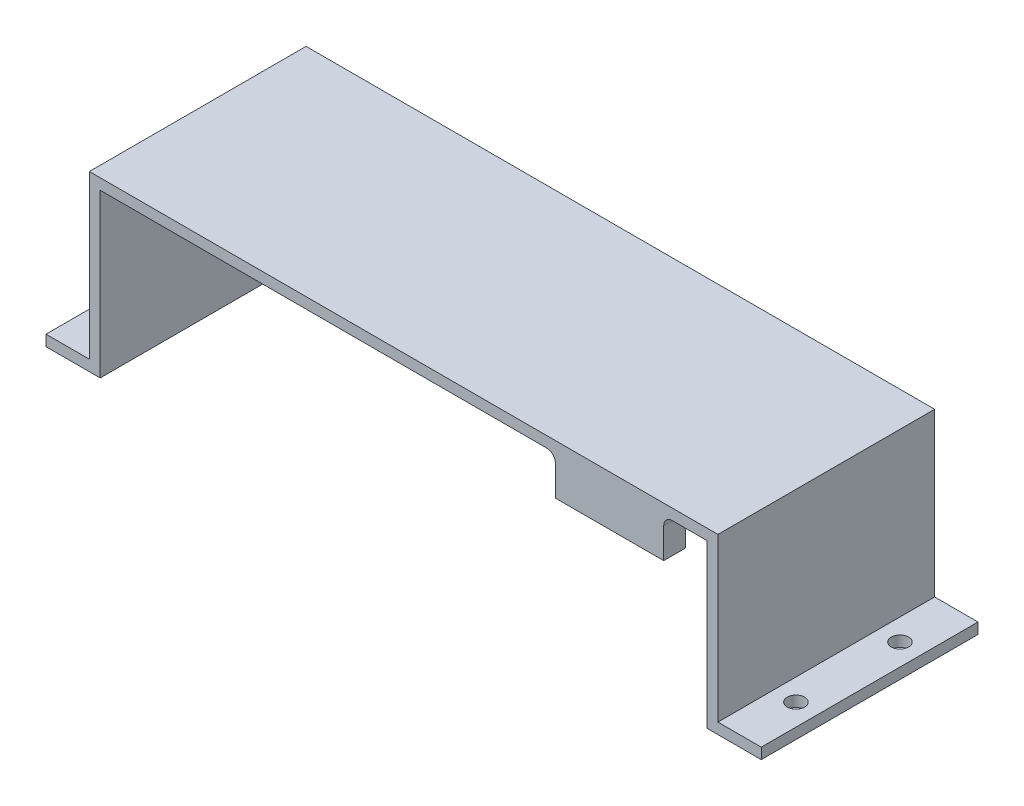
SolidWorks part; units mm, degrees
other "Markup1"
sketch "Sketch8" plane through (104.775, 3.175, 31.75) normal (0.0545, 0.0227, 0.9983) x (-0.9792, -0.1942, 0.0579)
ref_plane "Front Plane" through (0, 0, 0) normal (0, 0, 1) x (1, 0, 0)
ref_plane "Top Plane" through (0, 0, 0) normal (0, 1, 0) x (1, 0, 0)
ref_plane "Right Plane" through (0, 0, 0) normal (1, 0, 0) x (0, 0, -1)
sketch "Sketch1" plane through (0, 0, 0) normal (0, 1, 0) x (1, 0, 0)
  line L1 (-88.9, 31.75) -> (88.9, 31.75)
  line L2 (-88.9, 31.75) -> (-88.9, -31.75)
  line L3 (-88.9, -31.75) -> (88.9, -31.75)
  line L4 (88.9, 31.75) -> (88.9, -31.75)
  line L5 (-88.9, 31.75) -> (88.9, -31.75) construction
  line L6 (-88.9, -31.75) -> (88.9, 31.75) construction
  point P0 (0, 0)
  dimension "D1" = 177.8
  dimension "D2" = 63.5
extrude "Boss-Extrude1" add sketch "Sketch1" along normal blind 3.175
sketch "Sketch3" plane through (0, 3.175, 0) normal (0, 1, 0) x (1, 0, 0)
  line L0 (-88.9, -31.75) -> (88.9, -31.75) construction
  line L1 (-88.9, 31.75) -> (-92.075, 31.75)
  line L2 (-88.9, 31.75) -> (-88.9, -31.75)
  line L3 (-88.9, -31.75) -> (-92.075, -31.75)
  line L4 (-92.075, 31.75) -> (-92.075, -31.75)
  line L5 (0, -20.955) -> (0, 20.955) construction
  line L6 (88.9, -31.75) -> (92.075, -31.75)
  line L7 (92.075, 31.75) -> (92.075, -31.75)
  line L8 (88.9, 31.75) -> (92.075, 31.75)
  line L9 (88.9, 31.75) -> (88.9, -31.75)
  dimension "D1" = 3.175
extrude "Boss-Extrude2" add sketch "Sketch3" against normal blind 50.8
sketch "Sketch4" plane through (92.075, 0, 0) normal (1, 0, 0) x (0, 0, -1)
  line L0 (31.75, -47.625) -> (31.75, 3.175) construction
  line L1 (-31.75, -47.625) -> (31.75, -47.625)
  line L2 (-31.75, -47.625) -> (-31.75, -44.45)
  line L3 (-31.75, -44.45) -> (31.75, -44.45)
  line L4 (31.75, -47.625) -> (31.75, -44.45)
  dimension "D1" = 3.175
extrude "Boss-Extrude3" add sketch "Sketch4" along normal blind 12.7
sketch "Sketch5" plane through (0, -47.625, 0) normal (0, -1, 0) x (1, 0, 0)
  line L1 (104.775, -31.75) -> (88.9, -31.75) construction
  line L3 (88.9, 0) -> (104.775, 0) construction
  line L4 (88.9, 31.75) -> (88.9, -31.75) construction
  line L5 (104.775, 31.75) -> (104.775, -31.75) construction
  circle A0 centre (98.425, -15.24) radius 2.54
  circle A1 centre (98.425, 15.24) radius 2.54
  dimension "D1" = 5.08
  dimension "D2" = 6.35
  dimension "D3" = 16.51
extrude "Cut-Extrude1" cut sketch "Sketch5" against normal blind 12.7
mirror "Mirror1" about plane through (0, 0, 0) normal (1, 0, 0) of "Boss-Extrude3", "Cut-Extrude1"
sketch "Sketch6" plane through (0, 0, 31.75) normal (0, 0, 1) x (1, 0, 0)
  line L14 (-88.9, 0) -> (88.9, 0) construction
  line L15 (44.45, 0) -> (76.2, 0)
  line L16 (44.45, 0) -> (44.45, -11.43)
  line L17 (44.45, -11.43) -> (76.2, -11.43)
  line L18 (76.2, 0) -> (76.2, -11.43)
  line L19 (-88.9, -47.625) -> (-88.9, 0) construction
  dimension "D1" = 11.43
  dimension "D2" = 31.75
  dimension "D3" = 165.1
extrude "Boss-Extrude4" add sketch "Sketch6" against normal blind 6.35
fillet "Fillet1" radius 2.54 2 edges at (76.2, 0, 28.575) (44.45, 0, 28.575)
